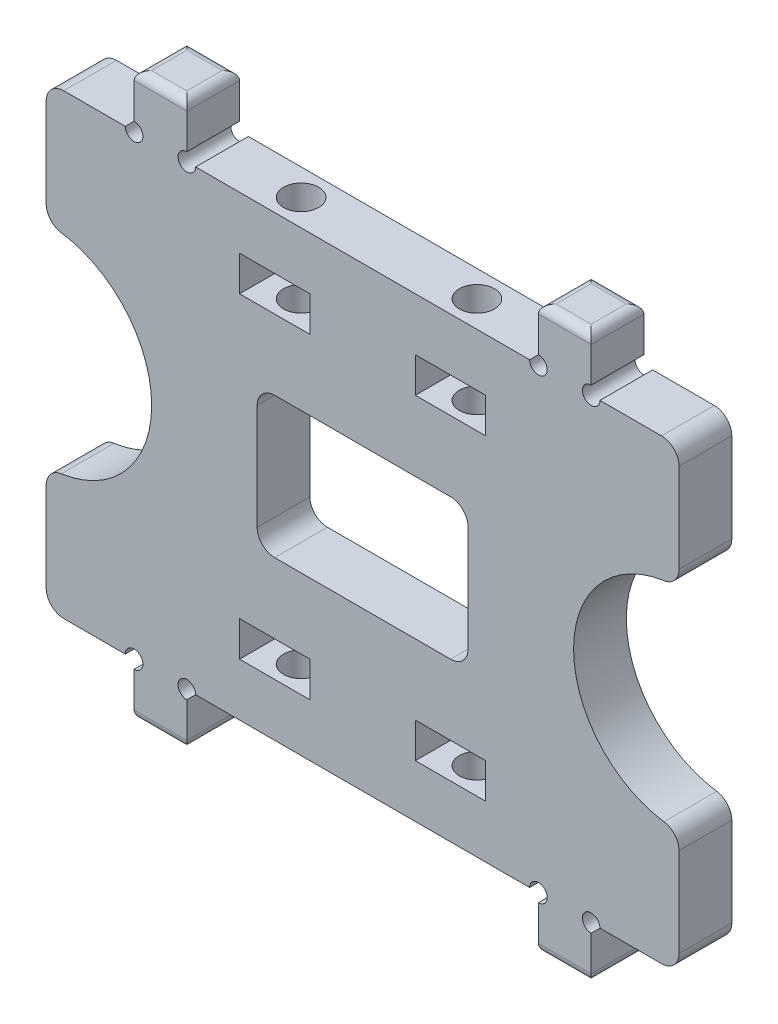
SolidWorks part; units mm, degrees
ref_plane "Front Plane" through (0, 0, 0) normal (0, 0, 1) x (1, 0, 0)
ref_plane "Top Plane" through (0, 0, 0) normal (0, 1, 0) x (1, 0, 0)
ref_plane "Right Plane" through (0, 0, 0) normal (1, 0, 0) x (0, 0, -1)
sketch "Sketch1" plane through (0, 0, 0) normal (0, 0, 1) x (1, 0, 0)
  line L1 (0, 0) -> (9.5, 0)
  line L2 (0, 0) -> (0, 9)
  line L6 (10, -0.5) -> (10, -3)
  line L7 (10, -3) -> (13, -3)
  line L8 (13, -0.5) -> (13, -3)
  line L9 (3, 5) -> (7, 5)
  line L10 (3, 5) -> (3, 3)
  line L11 (3, 3) -> (7, 3)
  line L12 (7, 5) -> (7, 3)
  line L13 (13.5, 0) -> (18, 0)
  line L14 (0, 0) -> (10.5, 0)
  line L15 (0, 0) -> (0, 13)
  line L16 (4.6188, 13) -> (12, 13)
  line L17 (18, 0) -> (18, 7)
  line L23 (0, 9) -> (2.3094, 9)
  line L24 (2.3094, 9) -> (4.6188, 13)
  line L25 (-2.3094, 17) -> (-3.4641, 15) [skipped]
  line L26 (-4.6188, 13) -> (-3.4641, 11) [skipped]
  line L27 (2.3094, 17) -> (0, 17) [skipped]
  line L28 (4.6188, 13) -> (3.4641, 15) [skipped]
  arc A0 (13.5, 0) -> (13, -0.5) centre (13, 0) ccw
  arc A1 (10, -0.5) -> (9.5, 0) centre (10, 0) ccw
  circle A3 centre (0, 13) radius 4 construction
  arc A4 (12, 13) -> (18, 7) centre (18, 13) ccw
  point P13 (5, 3)
  dimension "D10" = 8
  dimension "D1" = 13
  dimension "D2" = 18
  dimension "D3" = 10
  dimension "D4" = 3
  dimension "D5" = 3
  dimension "D6" = 5
  dimension "D7" = 4
  dimension "D8" = 2
  dimension "D9" = 3
extrude "Boss-Extrude1" add sketch "Sketch1" along normal blind 3 contours A4 L16 L24 L23 L2 L1 A1 L6 L7 L8 A0 L13 L17 L9 L12 L11 L10 region at (8.8378, 5.3438, 0)
sketch "Sketch2" plane through (0, 0, 0) normal (0, -1, 0) x (1, 0, 0)
  line L1 (0, 3) -> (0, 0) construction
  line L2 (0, 3) -> (9.5, 3) construction
  circle A0 centre (5, 1.5) radius 1
  dimension "D1" = 1.5
  dimension "D2" = 5
extrude "Cut-Extrude1" cut sketch "Sketch2" against normal blind 8 contours A0
fillet "Fillet1" radius 1 2 edges at (18, 7, 1.5) (18, 0, 1.5)
fillet "Fillet2" radius 0.5 4 edges at (10, -3, 1.5) (13, -3, 1.5) (11.5, -3, 0) (11.5, -3, 3)
mirror "Mirror1" about plane through (0, 0, 3) normal (-1, 0, 0) of bodies 102
mirror "Mirror2" about plane through (0, 13, 3) normal (0, 1, 0) of bodies 103
sketch "Sketch3" plane through (0, 0, 0) normal (0, 0, -1) x (-1, 0, 0)
  line L0 (9.5, 26) -> (-9.5, 26) construction
  line L1 (-6, 17) -> (6, 17)
  line L2 (-6, 17) -> (-6, 9)
  line L3 (-6, 9) -> (6, 9)
  line L4 (6, 17) -> (6, 9)
  arc A0 (17.1429, 18.9385) -> (17.1429, 7.0615) centre (18, 13) ccw construction
  point P4 (6, 13)
  point P8 (12, 13)
  point P9 (0, 17)
  point P12 (0, 26)
  dimension "D1" = 12
  dimension "D2" = 8
  dimension "D3" = 0
  dimension "D4" = 0
extrude "Cut-Extrude2" cut sketch "Sketch3" against normal blind 10
fillet "Fillet3" radius 1 4 edges at (6, 9, 1.5) (-6, 9, 1.5) (-6, 17, 1.5) (6, 17, 1.5)
